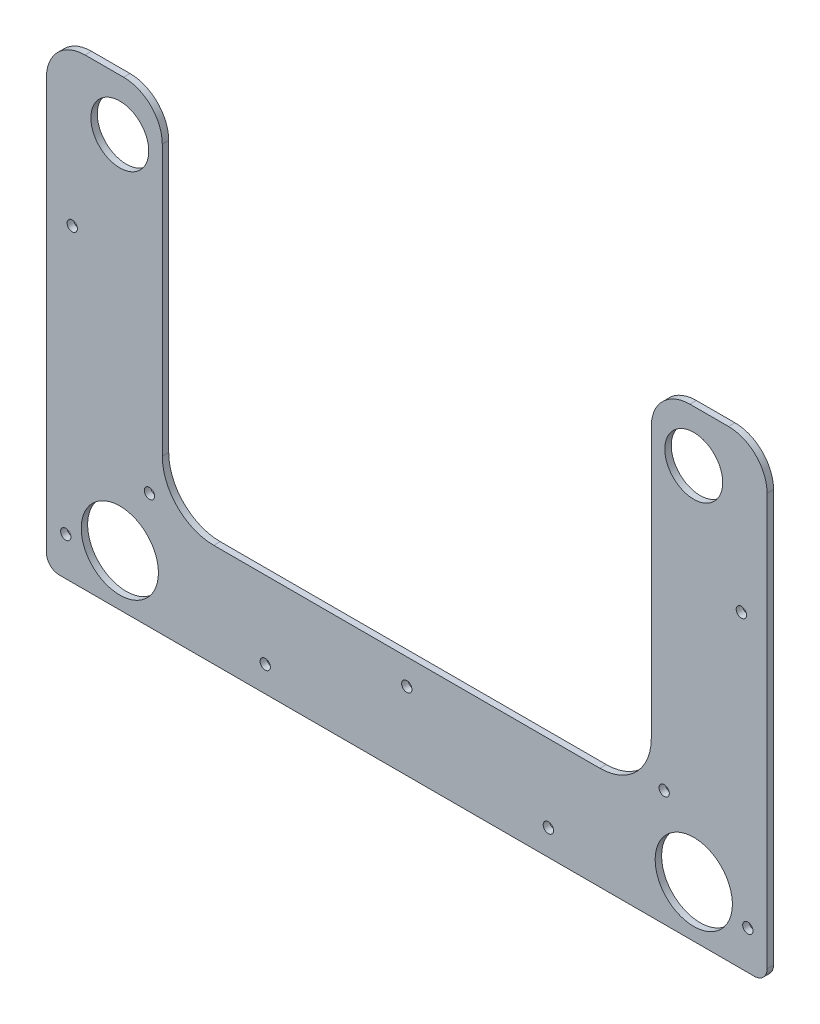
SolidWorks part; units mm, degrees
ref_plane "Front Plane" through (0, 0, 0) normal (0, 0, 1) x (1, 0, 0)
ref_plane "Top Plane" through (0, 0, 0) normal (0, 1, 0) x (1, 0, 0)
ref_plane "Right Plane" through (0, 0, 0) normal (1, 0, 0) x (0, 0, -1)
sketch "Sketch1" plane through (0, 0, 0) normal (0, 0, 1) x (1, 0, 0)
  line L5 (120.65, -152.4) -> (120.65, -6.35)
  line L6 (127, 0) -> (171.45, 0) construction
  line L7 (177.8, -6.35) -> (177.8, -222.25)
  line L10 (0, -206.2199) -> (0, -63.6275) construction
  line L11 (-54.9244, 0) -> (300.6756, 0) construction
  line L13 (12.7, -177.8) -> (95.25, -177.8)
  line L14 (12.7, -228.6) -> (171.45, -228.6)
  line L15 (141.605, -25.4) -> (141.605, -84.2822) construction
  line L16 (141.605, -25.4) -> (141.605, -127) construction
  line L19 (-141.605, -19.05) -> (-141.605, -77.9322) construction
  line L20 (141.605, -25.4) -> (141.605, -203.2) construction
  line L22 (-120.65, -152.4) -> (-120.65, -6.35)
  line L23 (-12.7, -177.8) -> (-95.25, -177.8)
  line L24 (-12.7, -228.6) -> (-171.45, -228.6)
  line L25 (-177.8, -6.35) -> (-177.8, -222.25)
  line L26 (-12.7, -177.8) -> (12.7, -177.8)
  line L27 (-12.7, -228.6) -> (12.7, -228.6)
  line L28 (-177.8, -6.35) -> (-177.8, 6.35)
  line L29 (-165.1, 19.05) -> (-133.35, 19.05)
  line L30 (-120.65, 6.35) -> (-120.65, -6.35)
  line L31 (120.65, 6.35) -> (120.65, -6.35)
  line L32 (177.8, -6.35) -> (177.8, 6.35)
  line L33 (165.1, 19.05) -> (133.35, 19.05)
  arc A0 (95.25, -177.8) -> (120.65, -152.4) centre (95.25, -152.4) ccw
  arc A4 (120.65, -6.35) -> (127, 0) centre (127, -6.35) cw construction
  circle A8 centre (141.605, -25.4) radius 14.2875
  circle A9 centre (141.605, -25.4) radius 38.1 construction
  arc A10 (177.8, -6.35) -> (171.45, 0) centre (171.45, -6.35) ccw construction
  arc A11 (171.45, -228.6) -> (177.8, -222.25) centre (171.45, -222.25) ccw
  arc A14 (141.605, -82.55) -> (120.9214, -78.6758) centre (141.605, -25.4) ccw construction
  arc A15 (-141.605, -82.55) -> (-120.9214, -78.6758) centre (-141.605, -25.4) cw construction
  circle A16 centre (-141.605, -25.4) radius 38.1 construction
  circle A17 centre (-141.605, -25.4) radius 14.2875
  arc A19 (-95.25, -177.8) -> (-120.65, -152.4) centre (-95.25, -152.4) cw
  circle A20 centre (141.605, -127) radius 38.1 construction
  circle A21 centre (-141.605, -127) radius 38.1 construction
  arc A23 (-171.45, -228.6) -> (-177.8, -222.25) centre (-171.45, -222.25) cw
  circle A24 centre (-141.605, -203.2) radius 19.05
  circle A37 centre (141.605, -203.2) radius 19.05
  circle A39 centre (-69.85, -215.9) radius 2.54
  circle A40 centre (69.85, -215.9) radius 2.54
  circle A42 centre (0, -190.5) radius 2.54
  arc A44 (-133.35, 19.05) -> (-120.65, 6.35) centre (-133.35, 6.35) cw
  arc A45 (-177.8, 6.35) -> (-165.1, 19.05) centre (-165.1, 6.35) cw
  arc A46 (133.35, 19.05) -> (120.65, 6.35) centre (133.35, 6.35) ccw
  arc A47 (177.8, 6.35) -> (165.1, 19.05) centre (165.1, 6.35) ccw
  circle A50 centre (-149.225, 6.35) radius 2.54
  circle A53 centre (149.225, 6.35) radius 2.54
  circle A54 centre (-168.275, -209.55) radius 2.54
  circle A56 centre (168.275, -209.55) radius 2.54
  circle A58 centre (-165.1, -76.2) radius 2.54
  circle A59 centre (165.1, -76.2) radius 2.54
  circle A60 centre (-127, -171.45) radius 2.54
  circle A61 centre (127, -171.45) radius 2.54
  point P2 (177.8, -44.45)
  point P18 (177.8, 0)
  point P23 (177.8, -228.6)
  point P24 (177.8, -228.6)
  point P31 (177.8, 0)
  point P48 (-177.8, 0)
  point P49 (-177.8, -228.6)
  point P51 (-177.8, -44.45)
  point P78 (-141.605, -203.2)
  dimension "D6" = 25.4
  dimension "D7" = 6.35
  dimension "D8" = 6.35
  dimension "D9" = 177.8
  dimension "D10" = 28.575
  dimension "D12" = 76.2
  dimension "D13" = 57.15
  dimension "D15" = 38.1
  dimension "D18" = 76.2
  dimension "D21" = 5.08
  dimension "D29" = 9.525
  dimension "D32" = 5.08
  dimension "D35" = 5.08
  dimension "D40" = 12.7
  dimension "D43" = 5.08
  dimension "D45" = 12.7
  dimension "D30" = 5.08
  dimension "D41" = 5.08
  dimension "D22" = 6.35
  dimension "D2" = 120.65
  dimension "D3" = 177.8
  dimension "D4" = 228.6
  dimension "D5" = 177.8
  dimension "D11" = 20.955
  dimension "`" = 25.4
  dimension "D14" = 57.15
  dimension "D16" = 184.15
  dimension "D17" = 101.6
  dimension "D19" = 25.4
  dimension "D20" = 107.95
  dimension "D23" = 57.15
  dimension "D26" = 19.05
  dimension "D27" = 25.4
  dimension "D28" = 25.4
  dimension "D33" = 12.7
  dimension "D34" = 12.7
  dimension "D36" = 12.7
  dimension "D39" = 19.05
  dimension "D44" = 28.575
  dimension "D24" = 95.25
extrude "Boss-Extrude3" add sketch "Sketch1" along normal blind 3.175
sketch "Sketch2" plane through (0, 0, 3.175) normal (0, 0, 1) x (1, 0, 0)
  line L0 (177.8, -222.25) -> (177.8, 6.35) construction
  line L1 (-177.8, 19.05) -> (177.8, 19.05)
  line L2 (-177.8, 19.05) -> (-177.8, 0)
  line L3 (-177.8, 0) -> (177.8, 0)
  line L4 (177.8, 19.05) -> (177.8, 0)
  line L5 (-177.8, 6.35) -> (-177.8, -222.25) construction
  line L7 (-133.35, 19.05) -> (-165.1, 19.05) construction
  dimension "D1" = 19.05
extrude "Cut-Extrude1" cut sketch "Sketch2" against normal through all
fillet "Fillet1" radius 19.05 4 edges at (177.8, 0, 1.5875) (120.65, 0, 1.5875) (-120.65, 0, 1.5875) (-177.8, 0, 1.5875)
